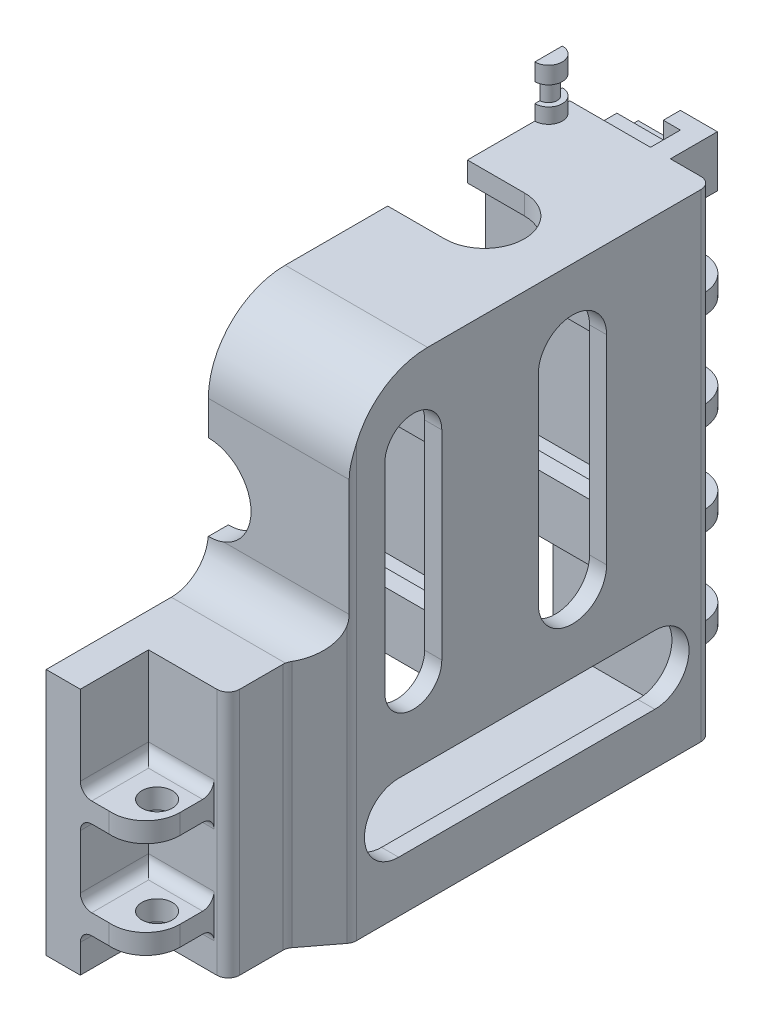
SolidWorks part; units mm, degrees
other "Marca1"
sketch "Croquis36" plane through (80, 81, -87.96) normal (0.1619, 0.9849, -0.0617) x (0.0148, -0.0649, -0.9978)
ref_plane "Front Plane" through (0, 0, 0) normal (0, 0, 1) x (1, 0, 0)
ref_plane "Top Plane" through (0, 0, 0) normal (0, 1, 0) x (1, 0, 0)
ref_plane "Right Plane" through (0, 0, 0) normal (1, 0, 0) x (0, 0, -1)
sketch "Croquis13" plane through (0, 0, 0) normal (0, 1, 0) x (1, 0, 0)
  line L0 (0, 80) -> (23, 80)
  line L1 (25, 78) -> (25, 17.5)
  line L2 (24.5908, 16.2879) -> (20.4092, 10.7997)
  line L3 (20, 9.5876) -> (20, 2)
  line L4 (18, 0) -> (0, 0)
  line L5 (0, 77) -> (22, 77)
  line L6 (22, 77) -> (22, 17.8376)
  line L7 (22, 17.8376) -> (18.0229, 12.6179)
  line L8 (17, 9.5876) -> (17, 3)
  line L9 (17, 3) -> (0, 3)
  line L10 (0, 80) -> (0, 77)
  line L11 (0, 3) -> (0, 0)
  line L12 (0, 77) -> (0, 3)
  line L13 (22, 20) -> (25, 20)
  arc A0 (20, 2) -> (18, 0) centre (18, 2) cw
  arc A1 (20.4092, 10.7997) -> (20, 9.5876) centre (22, 9.5876) ccw
  arc A2 (25, 17.5) -> (24.5908, 16.2879) centre (23, 17.5) cw
  arc A3 (23, 80) -> (25, 78) centre (23, 78) cw
  arc A4 (22, 77) -> (22, 77) centre (22, 77) cw
  arc A5 (22, 17.8376) -> (22, 17.8376) centre (22, 17.8376) cw
  arc A6 (18.0229, 12.6179) -> (17, 9.5876) centre (22, 9.5876) ccw
  arc A7 (17, 3) -> (17, 3) centre (17, 3) cw
  dimension "D1" = 2
  dimension "D2" = 80
  dimension "D3" = 25
  dimension "D4" = 60
  dimension "D5" = 8.25
  dimension "D6" = 20
  dimension "D8" = 2.5
  dimension "D7" = 3
extrude "Saliente-Extruir1" add sketch "Croquis13" along normal blind 3 contours A7 L8 A6 L7 A5 L6 A4 L5 L12 L9 region at (10.6798, 0, -41.1375)
extrude "Saliente-Extruir2" add sketch "Croquis13<3>" along normal blind 80.5 contours L5 A4 L6 L13 L1 A3 L0 L10 region at (11.5, 0, -79.35)
sketch "Croquis13<3>" plane through (0, 0, 0) normal (0, 1, 0) x (1, 0, 0) same geometry as "Croquis13"
extrude "Saliente-Extruir3" add sketch "Croquis13<4>" along normal blind 40 contours L8 A7 L9 L11 L4 A0 L3 A1 L2 A2 L1 L13 L6 A5 L7 A6 region at (8.5, 0, -2.6798)
sketch "Croquis13<4>" plane through (0, 0, 0) normal (0, 1, 0) x (1, 0, 0) same geometry as "Croquis13"
fillet "Redondeo1" radius 10 2 edges at (23.5, 80.5, -20) (23.5, 40, -20)
sketch "Croquis14" plane through (0, 0, 0) normal (1, 0, 0) x (0, 0, -1)
  line L2 (2, 40) -> (0, 40) construction
  line L43 (2, 40) -> (0, 40)
  line L44 (9.5876, 40) -> (2, 40) construction
  line L45 (9.5876, 40) -> (2, 40)
  line L46 (20, 70.5) -> (20, 50) construction
  line L47 (10, 40) -> (9.5876, 40) construction
  line L48 (20, 70.5) -> (20, 50)
  line L49 (10, 40) -> (9.5876, 40)
  line L50 (78, 80.5) -> (30, 80.5) construction
  line L51 (78, 80.5) -> (30, 80.5)
  line L52 (80, 80.5) -> (78, 80.5) construction
  line L53 (80, 80.5) -> (78, 80.5)
  line L54 (80, 84) -> (78, 84)
  line L55 (78, 84) -> (30, 84)
  line L56 (16.5, 70.5) -> (16.5, 50)
  line L57 (10, 43.5) -> (9.5876, 43.5)
  line L58 (9.5876, 43.5) -> (2, 43.5)
  line L59 (2, 43.5) -> (0, 43.5)
  line L60 (0, 43.5) -> (0, 40)
  line L61 (80, 84) -> (80, 80.5)
  arc A24 (17.5, 43.3856) -> (20, 50) centre (10, 50) ccw construction
  arc A25 (16.2879, 42.2242) -> (17.5, 43.3856) centre (10, 50) ccw construction
  arc A26 (10.7997, 40.032) -> (16.2879, 42.2242) centre (10, 50) ccw construction
  arc A27 (10, 40) -> (10.7997, 40.032) centre (10, 50) ccw construction
  arc A28 (17.5, 43.3856) -> (20, 50) centre (10, 50) ccw
  arc A29 (16.2879, 42.2242) -> (17.5, 43.3856) centre (10, 50) ccw
  arc A30 (10.7997, 40.032) -> (16.2879, 42.2242) centre (10, 50) ccw
  arc A31 (10, 40) -> (10.7997, 40.032) centre (10, 50) ccw
  arc A32 (30, 80.5) -> (20, 70.5) centre (30, 70.5) ccw construction
  arc A33 (30, 80.5) -> (20, 70.5) centre (30, 70.5) ccw
  arc A34 (30, 84) -> (16.5, 70.5) centre (30, 70.5) ccw
  arc A35 (14.875, 45.7007) -> (16.5, 50) centre (10, 50) ccw
  arc A36 (14.0871, 44.9458) -> (14.875, 45.7007) centre (10, 50) ccw
  arc A37 (10.5198, 43.5208) -> (14.0871, 44.9458) centre (10, 50) ccw
  arc A38 (10, 43.5) -> (10.5198, 43.5208) centre (10, 50) ccw
  dimension "D1" = 3.5
extrude "Saliente-Extruir4" add sketch "Croquis14" along normal up to surface (25 mm away) up to face at (25, 46.6755, -37.0762)
sketch "Croquis16" plane through (0, 0, 0) normal (1, 0, 0) x (0, 0, -1)
  line L0 (77, 3) -> (61.19, 3) construction
  line L1 (77, 3) -> (3, 3) construction
  line L2 (61.19, 3) -> (56.19, 3) construction
  line L3 (58.69, 3) -> (58.69, 19) construction
  line L4 (61.19, 3) -> (78.15, 3)
  line L5 (61.19, 3) -> (61.19, 19)
  line L6 (61.19, 19) -> (78.15, 19)
  line L7 (78.15, 3) -> (78.15, 19)
  line L8 (61.19, 19) -> (58.69, 19) construction
  line L9 (56.19, 3) -> (53.19, 3)
  line L12 (56.19, 3) -> (56.19, 19)
  line L13 (56.19, 19) -> (56.19, 80.5)
  line L15 (56.19, 19) -> (56.19, 3)
  line L16 (56.19, 3) -> (53.19, 3)
  line L17 (53.19, 80.5) -> (53.19, 3)
  line L18 (30, 80.5) -> (77, 80.5) construction
  line L19 (56.19, 80.5) -> (53.19, 80.5)
  dimension "D1" = 15.81
  dimension "D2" = 5
  dimension "D3" = 16.96
  dimension "D4" = 16
  dimension "D5" = 3
extrude "Saliente-Extruir5" add sketch "Croquis16" along normal up to surface (22 mm away) region at (0, 41.75, -54.69)
sketch "Croquis18" plane through (0, 0, 0) normal (1, 0, 0) x (0, 0, -1)
  line L34 (45.7, 80.5) -> (42.4, 80.5)
  line L35 (45.7, 80.5) -> (45.7, 29.9)
  line L36 (42.4, 68.7) -> (42.4, 36.7)
  line L37 (36.9, 68.7) -> (36.9, 65.5)
  line L38 (77, 80.5) -> (73.7, 80.5)
  line L39 (33.9, 29.9) -> (33.9, 39.9)
  line L40 (42.4, 36.7) -> (36.9, 36.7)
  line L41 (36.9, 36.7) -> (36.9, 39.9)
  line L42 (36.9, 39.9) -> (33.9, 39.9)
  line L43 (36.9, 65.5) -> (33.9, 65.5)
  line L44 (33.9, 65.5) -> (33.9, 80.5)
  line L45 (33.9, 80.5) -> (42.4, 80.5)
  line L46 (36.9, 68.7) -> (42.4, 68.7)
  line L47 (33.9, 29.9) -> (45.7, 29.9)
  line L48 (77, 80.5) -> (77, 29.9)
  line L49 (73.7, 68.7) -> (73.7, 36.7)
  line L50 (68.2, 68.7) -> (68.2, 65.5)
  line L51 (65.2, 29.9) -> (65.2, 39.9)
  line L52 (73.7, 36.7) -> (68.2, 36.7)
  line L53 (68.2, 36.7) -> (68.2, 39.9)
  line L54 (68.2, 39.9) -> (65.2, 39.9)
  line L55 (68.2, 65.5) -> (65.2, 65.5)
  line L56 (65.2, 65.5) -> (65.2, 80.5)
  line L57 (65.2, 80.5) -> (73.7, 80.5)
  line L58 (68.2, 68.7) -> (73.7, 68.7)
  line L59 (65.2, 29.9) -> (77, 29.9)
  line L61 (30, 80.5) -> (53.19, 80.5) construction
  line L62 (77, 80.5) -> (77, 3) construction
  dimension "D1" = 3.3
  dimension "D2" = 10
  dimension "D3" = 5.5
  dimension "D4" = 3.2
  dimension "D5" = 32
  dimension "D6" = 15
  dimension "D7" = 3.3
  dimension "D8" = 3
  dimension "D9" = 5.5
  dimension "D10" = 15
  dimension "D11" = 3.3
  dimension "D13" = 28
extrude "Saliente-Extruir7" add sketch "Croquis18" along normal up to surface (22 mm away) up to face at (22, 47.5968, -30.0727)
sketch "Croquis27" plane through (0, 0, -20) normal (0, 0, 1) x (1, 0, 0)
  circle A0 centre (0, 57) radius 7.5
  dimension "D1" = 57
  dimension "D2" = 15
extrude "Cortar-Extruir4" cut sketch "Croquis27" against normal blind 10 and the other way through all
sketch "Croquis29" plane through (0, 0, 0) normal (-1, 0, 0) x (0, 0, 1)
  line L0 (-53.19, 80.5) -> (-53.19, 3) construction
  line L1 (-56.19, 3) -> (-56.19, 80.5) construction
  line L2 (-53.19, 80.5) -> (-53.19, 3)
  line L3 (-56.19, 3) -> (-56.19, 80.5)
  line L4 (-56.19, 80.5) -> (-53.19, 80.5)
  line L5 (-56.19, 3) -> (-53.19, 3)
extrude "Cortar-Extruir5" cut sketch "Croquis29" against normal up to surface (22 mm away) up to face at (22, 46.3143, -67.67)
sketch "Croquis37" plane through (0, 40, 0) normal (0, -1, 0) x (1, 0, 0)
  line L2 (23, -80) -> (25, -80)
  line L3 (20.4092, -10.7997) -> (24.5908, -16.2879)
  line L4 (25, -17.5) -> (25, -10)
  line L5 (25, -10) -> (20.043, -10)
  line L6 (20.4092, -10.7997) -> (24.5908, -16.2879)
  line L7 (25, -17.5) -> (25, -10)
  line L8 (25, -10) -> (20.043, -10)
  line L9 (25, -80) -> (25, -78)
  line L10 (20, -2) -> (20, -9.5876)
  line L11 (20.043, -10) -> (25, -10)
  line L12 (25, -10) -> (25, 0)
  line L13 (25, 0) -> (18, 0)
  line L14 (20, -2) -> (20, -9.5876)
  line L15 (20.043, -10) -> (25, -10)
  line L16 (25, -10) -> (25, 0)
  line L19 (23, -80) -> (25, -80)
  line L20 (25, -80) -> (25, -78)
  line L23 (25, 0) -> (18, 0)
  arc A1 (23, -80) -> (25, -78) centre (23, -78) ccw
  arc A2 (20.043, -10) -> (20.4092, -10.7997) centre (22, -9.5876) ccw
  arc A3 (25, -17.5) -> (24.5908, -16.2879) centre (23, -17.5) ccw
  arc A4 (20.043, -10) -> (20.4092, -10.7997) centre (22, -9.5876) ccw
  arc A5 (25, -17.5) -> (24.5908, -16.2879) centre (23, -17.5) ccw
  arc A6 (20, -2) -> (18, 0) centre (18, -2) ccw
  arc A7 (20, -9.5876) -> (20.043, -10) centre (22, -9.5876) ccw
  arc A8 (20, -2) -> (18, 0) centre (18, -2) ccw
  arc A9 (20, -9.5876) -> (20.043, -10) centre (22, -9.5876) ccw
  arc A10 (23, -80) -> (25, -78) centre (23, -78) ccw
  arc M12 (18, 0) -> (20, -2) centre (18, -2) cw
  line M13 (20, -2) -> (20, -9.5876)
  arc M14 (20, -9.5876) -> (20.043, -10) centre (22, -9.5876) ccw
  line M15 (20.043, -10) -> (25, -10)
  line M16 (25, -10) -> (25, 0)
  line M17 (25, 0) -> (18, 0)
  dimension "D1" = 0
  dimension "D2" = 0
  dimension "D3" = 0
extrude "Cortar-Extruir6" cut sketch "Croquis37" against normal through all contours M17 M12 M13 M14 M15 M16 | A5 L7 A4 L6 M15 | A10 L20 L19 region at (23.2836, 40, -12.2954) region at (22.4505, 40, -4.9226)
sketch "Croquis38" plane through (0, 84, 0) normal (0, 1, 0) x (1, 0, 0)
  line L1 (0, 80) -> (17.65, 80)
  line L2 (0, 80) -> (0, 88.25)
  line L3 (0, 88.25) -> (17.65, 88.25)
  line L4 (17.65, 80) -> (17.65, 88.25)
  line L10 (14.15, 80) -> (14.15, 85.25)
  line L11 (14.15, 85.25) -> (11.15, 85.25)
  line L12 (11.15, 85.25) -> (11.15, 88.25)
  line L13 (0, 80) -> (0, 30) construction
  circle A1 centre (0, 76.25) radius 2.42
  line M6 (23, 80) -> (0, 80)
  line M7 (0, 80) -> (0, 30)
  dimension "D10" = 4.84
  dimension "D2" = 3.5
  dimension "D6" = 11.15
  dimension "D7" = 14.15
  dimension "D8" = 5.25
  dimension "D9" = 12
extrude "Saliente-Extruir8" add sketch "Croquis38" against normal blind 6 contours L12 L11 L10 L4 L3 M6 region at (15.1277, 84, -84.7488)
extrude "Saliente-Extruir9" add sketch "Croquis38<3>" against normal blind 3 from surface contours L12 L11 L10 L4 L3 M6 | L11 L12 L3 L2 L1 L10 region at (6.6093, 84, -83.9057) region at (15.1277, 84, -84.7488) starting at face at (14.3167, 78, -84.5)
sketch "Croquis38<3>" plane through (0, 84, 0) normal (0, 1, 0) x (1, 0, 0) same geometry as "Croquis38"
extrude "Saliente-Extruir10" add sketch "Croquis38<4>" along normal blind 9 contours A1 M7 region at (1.0271, 84, -76.25)
sketch "Croquis38<4>" plane through (0, 84, 0) normal (0, 1, 0) x (1, 0, 0) same geometry as "Croquis38"
sketch "Croquis39" plane through (0, 93, 0) normal (0, 1, 0) x (1, 0, 0)
  line L0 (0, 78.67) -> (0, 73.83) construction
  circle A0 centre (0, 76.25) radius 1.5
  circle A1 centre (0, 76.25) radius 2.42
  dimension "D1" = 3
extrude "Cortar-Extruir7" cut sketch "Croquis39" against normal blind 3.35 from offset 3 offset against normal yes
sketch "Croquis40" plane through (22, 0, 0) normal (-1, 0, 0) x (0, 0, 1)
  line L0 (-55.45, 70.2) -> (-55.45, 35.2) construction
  line L1 (-49.45, 70.2) -> (-49.45, 35.2)
  line L2 (-61.45, 70.2) -> (-61.45, 35.2)
  line L3 (-69.9188, 15) -> (-24.9188, 15) construction
  line L4 (-69.9188, 21) -> (-24.9188, 21)
  line L5 (-69.9188, 9) -> (-24.9188, 9)
  line L6 (-77, 3) -> (-17.8376, 3) construction
  line L7 (-65.2, 80.5) -> (-45.7, 80.5) construction
  line L8 (-73.7, 68.7) -> (-73.7, 36.7) construction
  line L9 (-27.5, 70.2) -> (-27.5, 35.2) construction
  line L10 (-22.5, 70.2) -> (-22.5, 35.2)
  line L11 (-32.5, 70.2) -> (-32.5, 35.2)
  line L12 (-20, 70.5) -> (-20, 50) construction
  arc A0 (-49.45, 70.2) -> (-61.45, 70.2) centre (-55.45, 70.2) ccw
  arc A1 (-61.45, 35.2) -> (-49.45, 35.2) centre (-55.45, 35.2) ccw
  arc A2 (-69.9188, 21) -> (-69.9188, 9) centre (-69.9188, 15) ccw
  arc A3 (-24.9188, 9) -> (-24.9188, 21) centre (-24.9188, 15) ccw
  arc A4 (-22.5, 70.2) -> (-32.5, 70.2) centre (-27.5, 70.2) ccw
  arc A5 (-32.5, 35.2) -> (-22.5, 35.2) centre (-27.5, 35.2) ccw
  point P2 (-55.45, 52.7)
  point P7 (-47.4188, 15)
  point P16 (-47.4188, 3)
  point P19 (-55.45, 80.5)
  point P24 (-73.7, 52.7)
  point P27 (-27.5, 52.7)
  dimension "D4" = 6
  dimension "D5" = 5
  dimension "D1" = 35
  dimension "D2" = 45
  dimension "D3" = 15
  dimension "D6" = 7.5
extrude "Cortar-Extruir8" cut sketch "Croquis40" against normal through all
sketch "Croquis41" plane through (0, 0, 0) normal (0, -1, 0) x (1, 0, 0)
  line L0 (17.5, 6) -> (17.5, 0) construction
  line L1 (6, 11.9791) -> (11, 11.9791)
  line L2 (17.5, 0) -> (6, 0)
  line L3 (6, 0) -> (6, 11.9791)
  line L4 (17.5, 6) -> (17.5, 0)
  line L5 (0, -80) -> (0, 0) construction
  line L6 (0, -40) -> (25, -40) construction
  line L7 (25, -78) -> (25, -17.5) construction
  line L8 (6, -80) -> (6, -91.9791)
  line L9 (17.5, -80) -> (6, -80)
  line L10 (17.5, -86) -> (17.5, -80)
  line L11 (6, -91.9791) -> (11, -91.9791)
  line L12 (0, -91.9791) -> (6, -91.9791)
  line L13 (0, 0) -> (6, 0)
  line L14 (0, 0) -> (0, 11.9791)
  line L15 (0, 11.9791) -> (6, 11.9791)
  line L16 (6, 0) -> (6, 11.9791)
  line L17 (6, -80) -> (6, -91.9791)
  line L18 (0, -80) -> (6, -80)
  line L19 (0, -80) -> (0, -91.9791)
  arc A0 (11, 11.9791) -> (17.5, 6) centre (11.5, 6) cw
  arc A1 (11, -91.9791) -> (17.5, -86) centre (11.5, -86) ccw
  circle A3 centre (13.5, 6) radius 2.675
  circle A4 centre (13.5, -86) radius 2.675
  line M7 (18, 0) -> (0, 0)
  line M9 (0, -80) -> (23, -80)
  dimension "D4" = 6
  dimension "D7" = 5.35
  dimension "D1" = 5
  dimension "D2" = 6
  dimension "D3" = 11.5
  dimension "D5" = 6
  dimension "D8" = 4
extrude "Saliente-Extruir13" add sketch "Croquis41<5>" against normal up to surface (43.5 mm away) contours L15 L14 L3 M7 region at (3, 0, 5.9896) up to face at (13.0744, 43.5, -5.1957)
sketch "Croquis41<5>" plane through (0, 0, 0) normal (0, -1, 0) x (1, 0, 0) same geometry as "Croquis41"
extrude "Saliente-Extruir14" add sketch "Croquis41<6>" against normal up to surface (75 mm away) contours L19 L12 L8 M9 region at (3, 0, -85.9896) up to face at (8.825, 75, -84.125)
sketch "Croquis41<6>" plane through (0, 0, 0) normal (0, -1, 0) x (1, 0, 0) same geometry as "Croquis41"
extrude "Saliente-Extruir11" add sketch "Croquis41" against normal blind 3.5 from offset 7 contours A0 L1 L3 L4 M7 | L11 A1 L10 L8 M9 region at (8.5, 0, 11.8129) region at (11.75, 0, -80.1662) offset against normal yes
extrude "Saliente-Extruir12" add sketch "Croquis41<3>" against normal blind 3.5 from offset 24 contours A0 L1 L3 L4 M7 | L11 A1 L10 L8 M9 region at (8.5, 0, 11.8129) region at (11.75, 0, -80.1662) offset against normal yes
sketch "Croquis41<3>" plane through (0, 0, 0) normal (0, -1, 0) x (1, 0, 0) same geometry as "Croquis41"
extrude "Saliente-Extruir15" add sketch "Croquis41<7>" against normal blind 3.5 from offset 40 contours L11 A1 L10 L8 A4 M9 region at (11.75, 0, -80.1662) offset against normal yes
sketch "Croquis41<7>" plane through (0, 0, 0) normal (0, -1, 0) x (1, 0, 0) same geometry as "Croquis41"
extrude "Saliente-Extruir16" add sketch "Croquis41<8>" against normal blind 3.5 from offset 57 contours L11 A1 L10 L8 A4 M9 region at (11.75, 0, -80.1662) offset against normal yes
sketch "Croquis41<8>" plane through (0, 0, 0) normal (0, -1, 0) x (1, 0, 0) same geometry as "Croquis41"
fillet "Redondeo3" radius 2 24 edges at (6, 7, -85.9896) (11.75, 7, -80) (6, 24, -85.9896) (11.75, 24, -80) (6, 27.5, -85.9896) (6, 10.5, -85.9896) (11.75, 10.5, -80) (11.75, 27.5, -80) (6, 40, -85.9896) (11.75, 40, -80) (6, 57, -85.9896) (11.75, 57, -80) (6, 43.5, -85.9896) (11.75, 43.5, -80) (6, 60.5, -85.9896) (11.75, 60.5, -80) (11.75, 7, 0) (6, 7, 5.9896) (11.75, 10.5, 0) (6, 10.5, 5.9896) (11.75, 24, 0) (6, 24, 5.9896) (11.75, 27.5, 0) (6, 27.5, 5.9896)
sketch "Croquis42" plane through (0, 84, 0) normal (0, 1, 0) x (1, 0, 0)
  line L0 (-10, 55) -> (10, 55) construction
  line L1 (-10, 62) -> (10, 62)
  line L2 (-10, 48) -> (10, 48)
  line L3 (0, 73.83) -> (0, 30) construction
  arc A0 (-10, 62) -> (-10, 48) centre (-10, 55) ccw
  arc A1 (10, 48) -> (10, 62) centre (10, 55) ccw
  point P2 (0, 55)
  dimension "D1" = 7
  dimension "D2" = 55
  dimension "D3" = 20
extrude "Cortar-Extruir9" cut sketch "Croquis42" against normal up to next contours L1 A1 L2 A0
sketch "Croquis44" plane through (0, 0, 0) normal (0, -1, 0) x (1, 0, 0)
  line L0 (6, 0) -> (0, 0)
  line L1 (6, -80) -> (0, -80)
  line L10 (18, 0) -> (6, 0)
  line L11 (6, 0) -> (6, 11.9791)
  line L12 (6, 11.9791) -> (0, 11.9791)
  line L13 (0, 11.9791) -> (0, -91.9791)
  line L14 (0, -91.9791) -> (6, -91.9791)
  line L15 (6, -91.9791) -> (6, -80)
  line L16 (6, -80) -> (23, -80)
  line L17 (25, -78) -> (25, -17.5)
  line L18 (24.5908, -16.2879) -> (20.4092, -10.7997)
  line L19 (20, -9.5876) -> (20, -2)
  line L20 (18, 0) -> (6, 0)
  line L23 (0, 0) -> (0, -80)
  line L26 (6, -80) -> (23, -80)
  line L27 (25, -78) -> (25, -17.5)
  line L28 (24.5908, -16.2879) -> (20.4092, -10.7997)
  line L29 (20, -9.5876) -> (20, -2)
  arc A4 (23, -80) -> (25, -78) centre (23, -78) ccw
  arc A5 (25, -17.5) -> (24.5908, -16.2879) centre (23, -17.5) ccw
  arc A6 (20, -9.5876) -> (20.4092, -10.7997) centre (22, -9.5876) ccw
  arc A7 (20, -2) -> (18, 0) centre (18, -2) ccw
  arc A8 (23, -80) -> (25, -78) centre (23, -78) ccw
  arc A9 (25, -17.5) -> (24.5908, -16.2879) centre (23, -17.5) ccw
  arc A10 (20, -9.5876) -> (20.4092, -10.7997) centre (22, -9.5876) ccw
  arc A11 (20, -2) -> (18, 0) centre (18, -2) ccw
  dimension "D1" = 0
